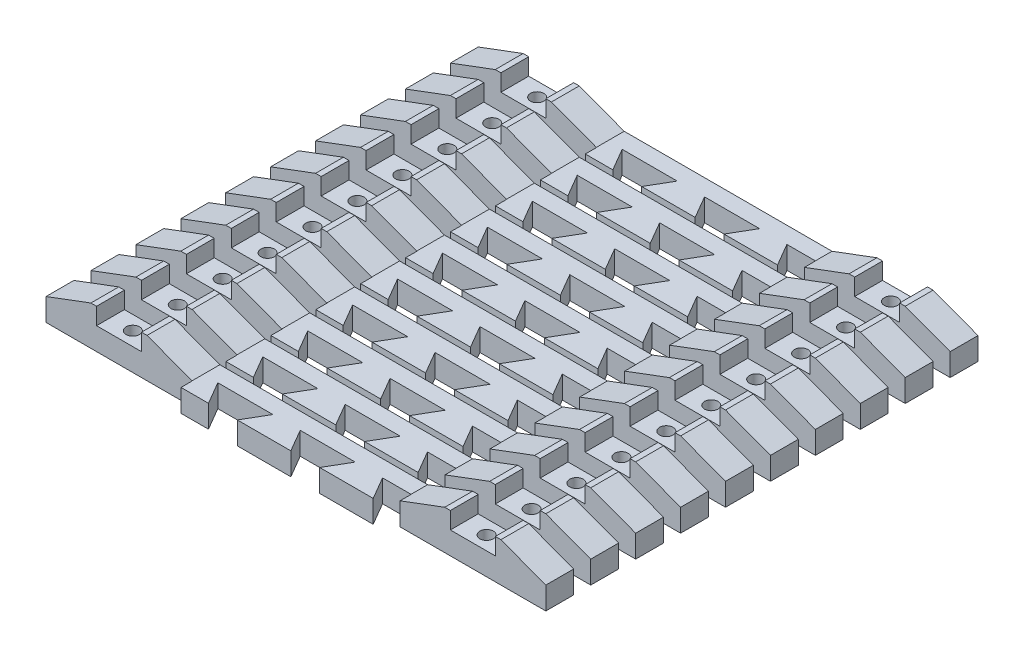
SolidWorks part; units mm, degrees
other "标注1"
sketch "草图3" plane through (-22.25, 4, -10) normal (-0.231, 0.6469, -0.7268) x (-0.9696, -0.2151, 0.1167)
ref_plane "前视基准面" through (0, 0, 0) normal (0, 0, 1) x (1, 0, 0)
ref_plane "上视基准面" through (0, 0, 0) normal (0, 1, 0) x (1, 0, 0)
ref_plane "右视基准面" through (0, 0, 0) normal (1, 0, 0) x (0, 0, -1)
other "Configuration Table"
sketch "草图4" plane through (0, 0, 0) normal (0, 0, 1) x (1, 0, 0)
  line L6 (8.5, -1.5) -> (17.75, -1.5)
  line L11 (17.75, -1.5) -> (17.75, -3.5)
  line L16 (17.75, -3.5) -> (-4.5, -3.5)
  line L17 (-4.5, -3.5) -> (-4.5, -1.5)
  line L19 (0, 0) -> (0, -1.5)
  line L20 (0, -1.5) -> (4, -1.5)
  line L21 (4, -1.5) -> (4, 0)
  line L26 (4, 0) -> (4.5, 0)
  line L27 (4.5, 0) -> (8.5, -1.5)
  line L28 (0, 0) -> (-0.5, 0)
  line L29 (-0.5, 0) -> (-4.5, -1.5)
  dimension "D2" = 4
  dimension "D4" = 0.5
  dimension "D5" = 2
  dimension "D6" = 2
  dimension "D7" = 4
  dimension "D8" = 1.5
  dimension "D9" = 4
  dimension "D10" = 22.25
extrude "凸台-拉伸1" add sketch "草图4" along normal blind 2.5 contours L28 L29 L17 L16 L11 L6 L27 L26 L21 L20 L19 | L19 | L21 region at (5.9579, -2.2764, 0)
sketch "草图5" plane through (0, -1.5, 0) normal (0, 1, 0) x (1, 0, 0)
  line L0 (0, 0) -> (4, -2.5) construction
  line L1 (0, -2.5) -> (0, 0) construction
  line L2 (0, -2.5) -> (4, -2.5) construction
  line L3 (4, -2.5) -> (4, 0) construction
  line L4 (0, 0) -> (4, 0) construction
  circle A0 centre (2, -1.25) radius 0.6
  circle A1 centre (2, -1.25) radius 1
  dimension "D1" = 1.2
  dimension "D2" = 2
extrude "切除-拉伸1" cut sketch "草图5" against normal through all contours A0
extrude "切除-拉伸2" cut sketch "草图5<3>" along normal blind 1 from surface contours A1 starting at face at (2, -3.5, 1.85)
sketch "草图5<3>" plane through (0, -1.5, 0) normal (0, 1, 0) x (1, 0, 0) same geometry as "草图5"
mirror "镜向1" about plane through (0, 0, 2.5) normal (0, 0, 1) of bodies 215 203
mirror "镜向2" about plane through (17.75, 0, 2.5) normal (1, 0, 0) of bodies 204
sketch "草图6" plane through (0, -1.5, 0) normal (0, 1, 0) x (1, 0, 0)
  line L1 (9.8333, -1.5) -> (11, -3.5)
  line L2 (11, -3.5) -> (13.5, -3.5) construction
  line L3 (18.3333, -3.5) -> (20.8333, -3.5) construction
  line L4 (9.8333, -1.5) -> (14.6667, -1.5)
  line L5 (14.6667, -1.5) -> (13.5, -3.5)
  line L6 (13.5, -3.5) -> (18.3333, -3.5)
  line L7 (18.3333, -3.5) -> (17.1667, -1.5)
  line L8 (17.1667, -1.5) -> (22, -1.5)
  line L9 (11, -3.5) -> (8.5, -3.5)
  line L10 (8.5, -5) -> (8.5, 0) construction
  line L11 (22, -1.5) -> (20.8333, -3.5)
  line L12 (20.8333, -3.5) -> (25.6667, -3.5)
  line L13 (25.6667, -3.5) -> (24.5, -1.5)
  line L14 (24.5, -1.5) -> (27, -1.5)
  line L15 (-4.5, -2.5) -> (8.5, -2.5)
  line L16 (14.6667, -1.5) -> (17.1667, -1.5) construction
  line L17 (22, -1.5) -> (24.5, -1.5) construction
  line L18 (12.25, -3.5) -> (12.25, -1.5) construction
  line L19 (27, -5) -> (27, 0) construction
  line L20 (8.5, -2.5) -> (12.25, -2.5) construction
  line L21 (-4.5, -5) -> (-4.5, 0) construction
  line L22 (8.5, -2.5) -> (8.5, -3.5)
  line L23 (27, -1.5) -> (27, -2.5)
  line L24 (27, -2.5) -> (40, -2.5)
  line L25 (40, -5) -> (40, 0) construction
  line L26 (-4.5, -2.5) -> (-4.5, 0)
  line L27 (-4.5, 0) -> (40, 0)
  line L28 (40, 0) -> (40, -2.5)
  line L29 (-4.5, -2.5) -> (-4.5, -5)
  line L30 (-4.5, -5) -> (40, -5)
  line L31 (40, -5) -> (40, -2.5)
  line M2 (8.5, 0) -> (8.5, -5)
  line M3 (8.5, -5) -> (27, -5)
  line M4 (27, -5) -> (27, 0)
  dimension "D1" = 2
  dimension "D2" = 2.5
extrude "切除-拉伸6" cut sketch "草图6" against normal through all both and the other way through all contours L29 L30 L15 M2 | L14 L13 L12 L11 L8 L7 L6 L5 L4 L1 L9 M2 M3 M4 | L30 L31 L24 M4 region at (17.8534, -1.5, 3.508) region at (2, -1.5, 3.75) region at (33.5, -1.5, 3.75)
sketch "草图7" plane through (0, -1.5, 0) normal (0, 1, 0) x (1, 0, 0)
  line L0 (-4.5, -2.48) -> (8.52, -2.48)
  line L1 (-4.5, -2.5) -> (-4.5, 0) construction
  line L2 (8.52, -2.48) -> (8.52, -3.48)
  line L3 (8.52, -3.48) -> (10.9652, -3.48)
  line L4 (10.9652, -3.48) -> (9.7985, -1.48)
  line L5 (9.7985, -1.48) -> (14.7015, -1.48)
  line L6 (14.7015, -1.48) -> (13.5348, -3.48)
  line L7 (13.5348, -3.48) -> (18.2985, -3.48)
  line L8 (18.2985, -3.48) -> (17.1318, -1.48)
  line L9 (17.1318, -1.48) -> (22.0348, -1.48)
  line L10 (22.0348, -1.48) -> (20.8682, -3.48)
  line L11 (20.8682, -3.48) -> (25.6318, -3.48)
  line L12 (25.6318, -3.48) -> (24.4652, -1.48)
  line L13 (24.4652, -1.48) -> (27.02, -1.48)
  line L14 (27.02, -1.48) -> (27.02, -2.48)
  line L15 (27.02, -2.48) -> (40, -2.48)
  line L16 (40, -2.5) -> (40, 0) construction
  line L17 (40, -2.5) -> (36, -2.5) construction
  line L18 (27, -2.5) -> (27, -1.5) construction
  line L19 (24.5, -1.5) -> (27, -1.5) construction
  line L21 (14.6667, -1.5) -> (13.5, -3.5) construction
  line L22 (20.8333, -3.5) -> (25.6667, -3.5) construction
  line L23 (8.5, -3.5) -> (8.5, -2.5) construction
  line L25 (9.8333, -1.5) -> (11, -3.5) construction
  line L26 (18.3333, -3.5) -> (17.1667, -1.5) construction
  line L27 (22, -1.5) -> (20.8333, -3.5) construction
  line L28 (25.6667, -3.5) -> (24.5, -1.5) construction
  line L29 (-4.5, -2.48) -> (-4.5, -2.5)
  line L30 (-4.5, -2.5) -> (8.5, -2.5)
  line L31 (8.5, -2.5) -> (8.5, -3.5)
  line L32 (8.5, -3.5) -> (11, -3.5)
  line L33 (11, -3.5) -> (9.8333, -1.5)
  line L34 (9.8333, -1.5) -> (14.6667, -1.5)
  line L35 (14.6667, -1.5) -> (13.5, -3.5)
  line L36 (13.5, -3.5) -> (18.3333, -3.5)
  line L37 (18.3333, -3.5) -> (17.1667, -1.5)
  line L38 (17.1667, -1.5) -> (22, -1.5)
  line L39 (22, -1.5) -> (20.8333, -3.5)
  line L40 (20.8333, -3.5) -> (25.6667, -3.5)
  line L41 (25.6667, -3.5) -> (24.5, -1.5)
  line L42 (24.5, -1.5) -> (27, -1.5)
  line L43 (27, -1.5) -> (27, -2.5)
  line L44 (27, -2.5) -> (40, -2.5)
  line L45 (40, -2.5) -> (40, -2.48)
  dimension "D1" = 0.02
  dimension "D2" = 0.02
  dimension "D3" = 0.02
  dimension "D4" = 0.02
  dimension "D5" = 0.02
  dimension "D6" = 0.02
  dimension "D7" = 0.02
  dimension "D8" = 0.02
  dimension "D9" = 0.02
  dimension "D10" = 0.02
extrude "切除-拉伸7" cut sketch "草图7" against normal through all both and the other way through all
pattern_linear "阵列(线性)1" count 10 spacing 4 along (0, 0, -1) of bodies 217
